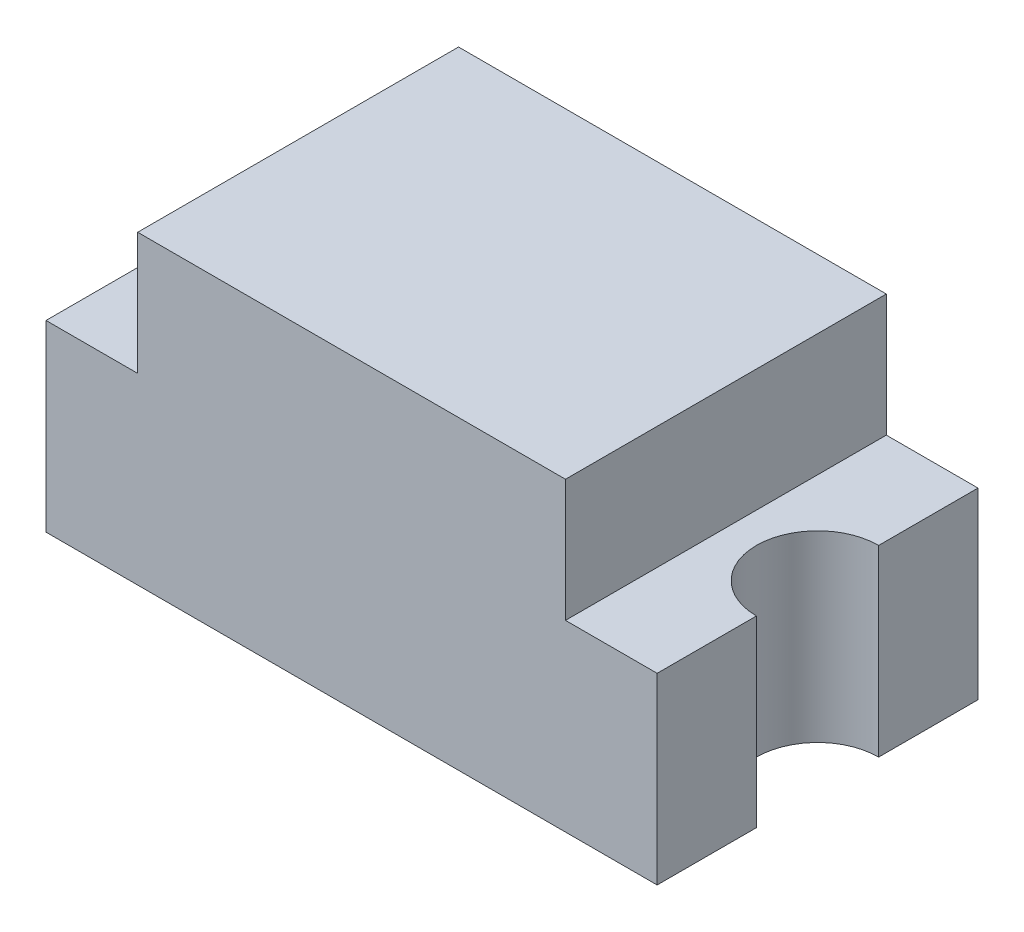
SolidWorks part; units mm, degrees
ref_plane "Front Plane" through (0, 0, 0) normal (0, 0, 1) x (1, 0, 0)
ref_plane "Top Plane" through (0, 0, 0) normal (0, 1, 0) x (1, 0, 0)
ref_plane "Right Plane" through (0, 0, 0) normal (1, 0, 0) x (0, 0, -1)
sketch "Sketch1" plane through (0, 0, 0) normal (0, 1, 0) x (1, 0, 0)
  line L1 (-1, -0.525) -> (1, -0.525)
  line L2 (-1, -0.525) -> (-1, 0.525)
  line L3 (-1, 0.525) -> (1, 0.525)
  line L4 (1, -0.525) -> (1, 0.525)
  line L5 (-1, -0.525) -> (1, 0.525) construction
  line L6 (-1, 0.525) -> (1, -0.525) construction
  circle A0 centre (1, 0) radius 0.2
  circle A1 centre (-1, 0) radius 0.2
  point P0 (0, 0)
  dimension "D3" = 0.4
  dimension "D1" = 2
  dimension "D2" = 1.05
extrude "Boss-Extrude1" add sketch "Sketch1" along normal blind 0.6 contours A1 L2 L1 L4 A0 L3 region at (0, 0, 0)
sketch "Sketch4" plane through (0, 0.6, 0) normal (0, 1, 0) x (1, 0, 0)
  line L0 (-1, 0.525) -> (1, 0.525) construction
  line L1 (-0.7, -0.525) -> (0.7, -0.525)
  line L2 (-0.7, -0.525) -> (-0.7, 0.525)
  line L3 (-0.7, 0.525) -> (0.7, 0.525)
  line L4 (0.7, -0.525) -> (0.7, 0.525)
  line L5 (-0.7, -0.525) -> (0.7, 0.525) construction
  line L6 (-0.7, 0.525) -> (0.7, -0.525) construction
  point P0 (0, 0)
  dimension "D1" = 1.4
extrude "Boss-Extrude3" add sketch "Sketch4" along normal blind 0.4
ref_point "Point1"
